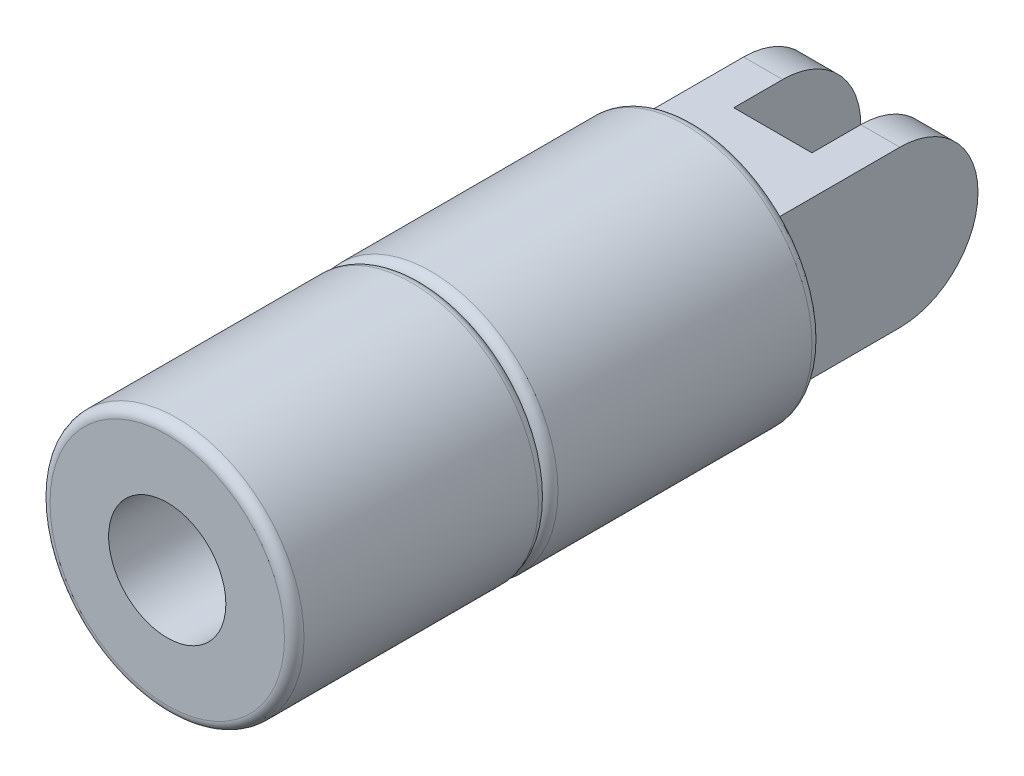
SolidWorks part; units mm, degrees
ref_plane "Front Plane" through (0, 0, 0) normal (0, 0, 1) x (1, 0, 0)
ref_plane "Top Plane" through (0, 0, 0) normal (0, 1, 0) x (1, 0, 0)
ref_plane "Right Plane" through (0, 0, 0) normal (1, 0, 0) x (0, 0, -1)
sketch "Sketch1" plane through (0, 0, 0) normal (0, 0, 1) x (1, 0, 0)
  circle A0 centre (0, 0) radius 6.5
  dimension "D1" = 13
extrude "Boss-Extrude1" add sketch "Sketch1" along normal blind 13
fillet "Fillet1" radius 0.5 2 edges at (6.5, 0, 0) (6.5, 0, 13)
sketch "Sketch2" plane through (0, 0, 13) normal (0, 0, 1) x (1, 0, 0)
  circle A0 centre (0, 0) radius 3
  dimension "D1" = 6
extrude "Cut-Extrude1" cut sketch "Sketch2" against normal blind 6
sketch "Sketch3" plane through (0, 0, 0) normal (0, 0, -1) x (-1, 0, 0)
  circle A0 centre (0, 0) radius 6.5
  dimension "D1" = 13
extrude "Boss-Extrude2" add sketch "Sketch3" along normal blind 14
fillet "Fillet2" radius 0.5 2 edges at (-6.5, 0, -14) (-6.5, 0, 0)
sketch "Sketch4" plane through (0, 0, -14) normal (0, 0, -1) x (-1, 0, 0)
  line L1 (-4, -4) -> (4, -4)
  line L2 (-4, -4) -> (-4, 4)
  line L3 (-4, 4) -> (4, 4)
  line L4 (4, -4) -> (4, 4)
  line L5 (-4, -4) -> (4, 4) construction
  line L6 (-4, 4) -> (4, -4) construction
  point P0 (0, 0)
  dimension "D1" = 8
  dimension "D2" = 8
extrude "Boss-Extrude3" add sketch "Sketch4" along normal blind 4
sketch "Sketch5" plane through (0, 0, -18) normal (0, 0, -1) x (-1, 0, 0)
  line L0 (-4, -4) -> (4, -4) construction
  line L1 (-4, 4) -> (-2, 4)
  line L2 (-4, 4) -> (-4, -4)
  line L3 (-4, -4) -> (-2, -4)
  line L4 (-2, 4) -> (-2, -4)
  line L5 (-4, -4) -> (4, -4) construction
  line L6 (4, 4) -> (2, 4)
  line L7 (4, 4) -> (4, -4)
  line L8 (4, -4) -> (2, -4)
  line L9 (2, 4) -> (2, -4)
  dimension "D1" = 2
  dimension "D2" = 2
extrude "Boss-Extrude4" add sketch "Sketch5" along normal blind 2.5
sketch "Sketch6" plane through (4, 0, 0) normal (1, 0, 0) x (0, 0, -1)
  line L0 (20.5, 4) -> (20.5, -4) construction
  circle A0 centre (20.5, 0) radius 4
extrude "Boss-Extrude5" add sketch "Sketch6" against normal blind 2
mirror "Mirror1" about plane through (0, 0, 0) normal (1, 0, 0) of "Boss-Extrude5"
